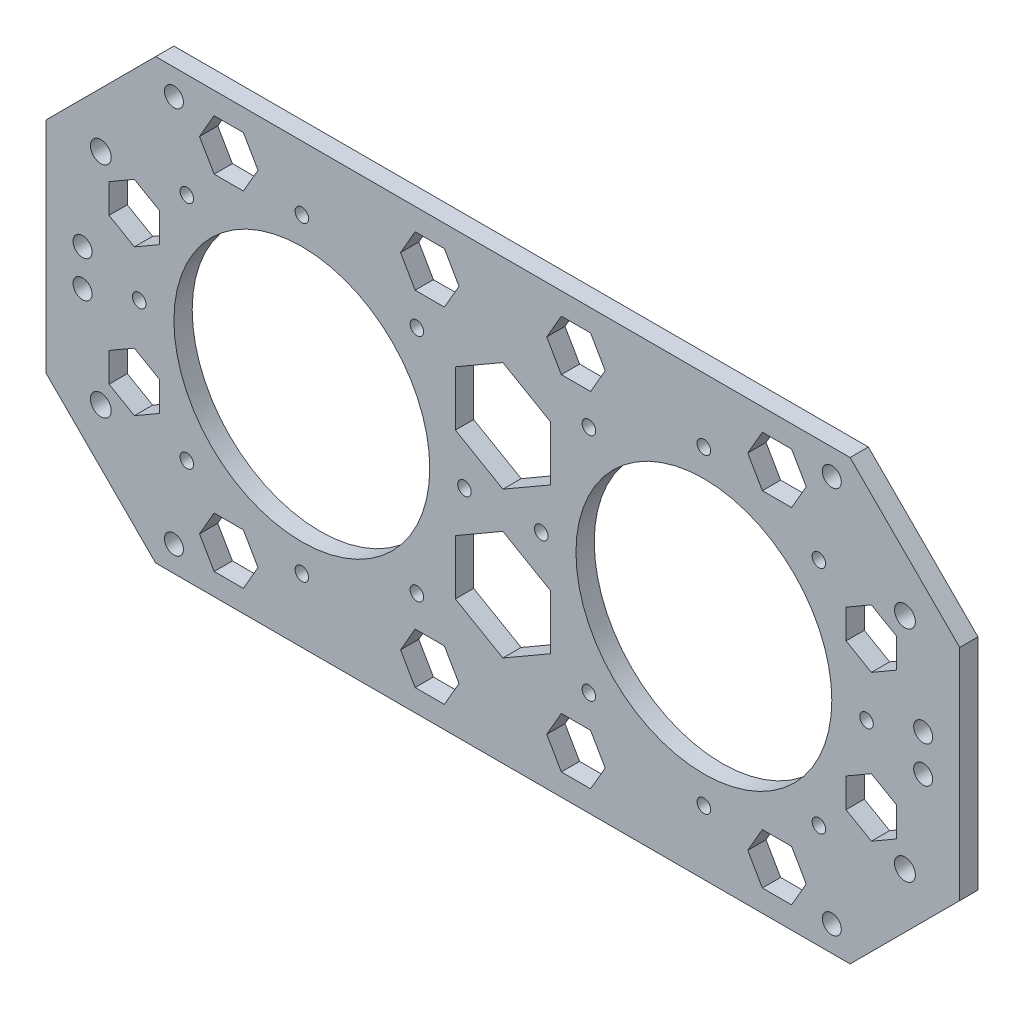
SolidWorks part; units mm, degrees
ref_plane "前视基准面" through (0, 0, 0) normal (0, 0, 1) x (1, 0, 0)
ref_plane "上视基准面" through (0, 0, 0) normal (0, 1, 0) x (1, 0, 0)
ref_plane "右视基准面" through (0, 0, 0) normal (1, 0, 0) x (0, 0, -1)
other "Configuration Table"
sketch "草图1" plane through (0, 0, 0) normal (0, 0, 1) x (1, 0, 0)
  line L1 (0, 0) -> (250, 0)
  line L2 (0, 0) -> (0, 120)
  line L3 (0, 120) -> (250, 120)
  line L4 (250, 0) -> (250, 120)
  circle A0 centre (70, 60) radius 35
  circle A1 centre (180, 60) radius 35
  dimension "D3" = 70
  dimension "D4" = 70
  dimension "D7" = 70
  dimension "D8" = 60
  dimension "D1" = 250
  dimension "D2" = 120
  dimension "D5" = 60
  dimension "D6" = 70
extrude "凸台-拉伸1" add sketch "草图1" along normal blind 5
sketch "草图2" plane through (0, 0, 5) normal (0, 0, 1) x (1, 0, 0)
  line L0 (125, 120) -> (125, 0) construction
  line L4 (0, 120) -> (0, 0)
  line L5 (0, 0) -> (250, 0)
  line L6 (250, 0) -> (250, 120)
  line L7 (250, 120) -> (0, 120)
  line L8 (0, 120) -> (0, 0)
  line L9 (0, 0) -> (250, 0)
  line L10 (250, 0) -> (250, 120)
  line L11 (250, 120) -> (0, 120)
  circle A0 centre (70, 102.5) radius 1.85
  circle A1 centre (70, 60) radius 35 construction
  circle A2 centre (70, 60) radius 35
  circle A3 centre (70, 17.5) radius 1.85
  circle A4 centre (25.5, 60) radius 1.85
  circle A5 centre (38.5337, 91.4663) radius 1.85
  circle A6 centre (70, 104.5) radius 1.85
  circle A7 centre (101.4663, 91.4663) radius 1.85
  circle A8 centre (114.5, 60) radius 1.85
  circle A9 centre (101.4663, 28.5337) radius 1.85
  circle A10 centre (70, 15.5) radius 1.85
  circle A11 centre (38.5337, 28.5337) radius 1.85
  circle A12 centre (180, 102.5) radius 1.85
  circle A13 centre (148.5337, 91.4663) radius 1.85
  circle A14 centre (135.5, 60) radius 1.85
  circle A15 centre (148.5337, 28.5337) radius 1.85
  circle A16 centre (180, 17.5) radius 1.85
  circle A17 centre (211.4663, 28.5337) radius 1.85
  circle A18 centre (224.5, 60) radius 1.85
  circle A19 centre (211.4663, 91.4663) radius 1.85
  point P14 (70, 60)
  point P30 (70, 60)
  dimension "D1" = 3.7
  dimension "D5" = 3.7
  dimension "D7" = 60
  dimension "D3" = 42.5
  dimension "D6" = 44.5
  dimension "D2" = 0
  dimension "D4" = 2
  dimension "D8" = 8
extrude "切除-拉伸1" cut sketch "草图2" against normal blind 10 contours A5 | A4 | A11 | A10 A3 | A3 A10 | A9 | A8 | A6 A0 | A0 A6 | A7 | A14 | A12 | A19 | A18 | A17 | A15 | A13 | A16 region at (70, 101.9688, 5) region at (70, 103.5, 5) region at (70, 18.0312, 5) region at (70, 16.5, 5) region at (25.5, 60, 5) region at (38.5337, 91.4663, 5) region at (101.4663, 91.4663, 5) region at (114.5, 60, 5) region at (101.4663, 28.5337, 5) region at (38.5337, 28.5337, 5) region at (180, 102.5, 5) region at (135.5, 60, 5) region at (148.5337, 28.5337, 5) region at (211.4663, 28.5337, 5) region at (224.5, 60, 5) region at (211.4663, 91.4663, 5)
sketch "草图3" plane through (0, 0, 5) normal (0, 0, 1) x (1, 0, 0)
  line L0 (30, 120) -> (0, 90)
  line L1 (125, 120) -> (125, 0)
  line L2 (0, 60) -> (250, 60)
  line L3 (220, 120) -> (250, 90)
  line L4 (0, 120) -> (0, 0)
  line L5 (0, 0) -> (250, 0)
  line L6 (250, 0) -> (250, 120)
  line L7 (250, 120) -> (0, 120)
  line L8 (0, 120) -> (0, 0)
  line L9 (0, 0) -> (250, 0)
  line L10 (250, 0) -> (250, 120)
  line L11 (250, 120) -> (0, 120)
  line L12 (220, 0) -> (250, 30)
  line L13 (30, 0) -> (0, 30)
  line M17 (0, 120) -> (0, 0)
  line M18 (0, 0) -> (250, 0)
  line M19 (250, 0) -> (250, 120)
  line M20 (250, 120) -> (0, 120)
  dimension "D2" = 45
  dimension "D3" = 30
  dimension "D1" = 0
extrude "切除-拉伸2" cut sketch "草图3" against normal blind 10 contours L0 M20 M17 | L13 L8 M18 | L12 L9 M19 | L3 M20 M19 region at (10, 110, 5) region at (240, 110, 5) region at (10, 10, 5) region at (240, 10, 5)
sketch "草图4" plane through (0, 0, 0) normal (0, 0, -1) x (-1, 0, 0)
  line L0 (-125, 120) -> (-125, 0) construction
  line L1 (-125, 65) -> (-112.0096, 72.5)
  line L2 (-112.0096, 72.5) -> (-112.0096, 87.5)
  line L3 (-112.0096, 87.5) -> (-125, 95)
  line L4 (-125, 95) -> (-137.9904, 87.5)
  line L5 (-137.9904, 87.5) -> (-137.9904, 72.5)
  line L6 (-137.9904, 72.5) -> (-125, 65)
  line L7 (-250, 60) -> (0, 60) construction
  line L8 (-220, 120) -> (-250, 90)
  line L9 (-250, 90) -> (-250, 30)
  line L10 (-250, 30) -> (-220, 0)
  line L11 (-220, 0) -> (-30, 0)
  line L12 (-30, 0) -> (0, 30)
  line L13 (0, 30) -> (0, 90)
  line L14 (0, 90) -> (-30, 120)
  line L15 (-30, 120) -> (-220, 120)
  line L16 (-220, 120) -> (-250, 90)
  line L17 (-250, 90) -> (-250, 30)
  line L18 (-250, 30) -> (-220, 0)
  line L19 (-220, 0) -> (-30, 0)
  line L20 (-30, 0) -> (0, 30)
  line L21 (0, 30) -> (0, 90)
  line L22 (0, 90) -> (-30, 120)
  line L23 (-30, 120) -> (-220, 120)
  line L24 (-109, 100.1436) -> (-113, 107.0718)
  line L25 (-137, 107.0718) -> (-141, 114)
  line L26 (-141, 114) -> (-149, 114)
  line L27 (-149, 114) -> (-153, 107.0718)
  line L28 (-153, 107.0718) -> (-149, 100.1436)
  line L29 (-149, 100.1436) -> (-141, 100.1436)
  line L30 (-141, 100.1436) -> (-137, 107.0718)
  line L31 (-101, 100.1436) -> (-109, 100.1436)
  line L32 (-97, 107.0718) -> (-101, 100.1436)
  line L33 (-101, 114) -> (-97, 107.0718)
  line L34 (-109, 114) -> (-101, 114)
  line L35 (-113, 107.0718) -> (-109, 114)
  line L36 (-137.9904, 47.5) -> (-125, 55)
  line L37 (-137.9904, 32.5) -> (-137.9904, 47.5)
  line L38 (-125, 25) -> (-137.9904, 32.5)
  line L39 (-112.0096, 32.5) -> (-125, 25)
  line L40 (-112.0096, 47.5) -> (-112.0096, 32.5)
  line L41 (-125, 55) -> (-112.0096, 47.5)
  line L42 (-101, 19.8564) -> (-109, 19.8564)
  line L43 (-97, 12.9282) -> (-101, 19.8564)
  line L44 (-101, 6) -> (-97, 12.9282)
  line L45 (-109, 6) -> (-101, 6)
  line L46 (-113, 12.9282) -> (-109, 6)
  line L47 (-109, 19.8564) -> (-113, 12.9282)
  line L48 (-141, 19.8564) -> (-137, 12.9282)
  line L49 (-149, 19.8564) -> (-141, 19.8564)
  line L50 (-153, 12.9282) -> (-149, 19.8564)
  line L51 (-149, 6) -> (-153, 12.9282)
  line L52 (-141, 6) -> (-149, 6)
  line L53 (-137, 12.9282) -> (-141, 6)
  circle A0 centre (-125, 80) radius 12.9904 construction
  circle A1 centre (-145, 107.0718) radius 6.9282 construction
  dimension "D2" = 15
  dimension "D3" = 40
  dimension "D4" = 6
  dimension "D5" = 8
  dimension "D6" = 20
  dimension "D1" = 0
extrude "切除-拉伸3" cut sketch "草图4" against normal blind 10 contours L25 L26 L27 L28 L29 L30 | L24 L35 L34 L33 L32 L31 | L1 L2 L3 L4 L5 L6 | L36 L41 L40 L39 L38 L37 | L48 L53 L52 L51 L50 L49 | L42 L47 L46 L45 L44 L43
sketch "草图6" plane through (0, 0, 5) normal (0, 0, 1) x (1, 0, 0)
  line L0 (220, 120) -> (250, 90) construction
  line L1 (250, 30) -> (250, 90) construction
  line L2 (220, 0) -> (250, 30) construction
  line L3 (30, 0) -> (220, 0) construction
  line L4 (220, 120) -> (30, 120) construction
  line L5 (30, 0) -> (0, 30) construction
  line L6 (141, 100.1436) -> (149, 100.1436)
  line L7 (137, 107.0718) -> (141, 100.1436)
  line L8 (141, 114) -> (137, 107.0718)
  line L9 (149, 114) -> (141, 114)
  line L10 (153, 107.0718) -> (149, 114)
  line L11 (149, 100.1436) -> (153, 107.0718)
  line L12 (141, 100.1436) -> (149, 100.1436)
  line L13 (137, 107.0718) -> (141, 100.1436)
  line L14 (141, 114) -> (137, 107.0718)
  line L15 (149, 114) -> (141, 114)
  line L16 (153, 107.0718) -> (149, 114)
  line L17 (149, 100.1436) -> (153, 107.0718)
  line L18 (97, 12.9282) -> (101, 6)
  line L19 (101, 19.8564) -> (97, 12.9282)
  line L20 (109, 19.8564) -> (101, 19.8564)
  line L21 (113, 12.9282) -> (109, 19.8564)
  line L22 (109, 6) -> (113, 12.9282)
  line L23 (101, 6) -> (109, 6)
  line L24 (97, 12.9282) -> (101, 6)
  line L25 (101, 19.8564) -> (97, 12.9282)
  line L26 (109, 19.8564) -> (101, 19.8564)
  line L27 (113, 12.9282) -> (109, 19.8564)
  line L28 (109, 6) -> (113, 12.9282)
  line L29 (101, 6) -> (109, 6)
  line L30 (149, 19.8564) -> (141, 19.8564)
  line L31 (153, 12.9282) -> (149, 19.8564)
  line L32 (149, 6) -> (153, 12.9282)
  line L33 (141, 6) -> (149, 6)
  line L34 (137, 12.9282) -> (141, 6)
  line L35 (141, 19.8564) -> (137, 12.9282)
  line L36 (149, 19.8564) -> (141, 19.8564)
  line L37 (153, 12.9282) -> (149, 19.8564)
  line L38 (149, 6) -> (153, 12.9282)
  line L39 (141, 6) -> (149, 6)
  line L40 (137, 12.9282) -> (141, 6)
  line L41 (141, 19.8564) -> (137, 12.9282)
  line L42 (137.9904, 32.5) -> (137.9904, 47.5)
  line L43 (125, 25) -> (137.9904, 32.5)
  line L44 (112.0096, 32.5) -> (125, 25)
  line L45 (112.0096, 47.5) -> (112.0096, 32.5)
  line L46 (125, 55) -> (112.0096, 47.5)
  line L47 (137.9904, 47.5) -> (125, 55)
  line L48 (137.9904, 32.5) -> (137.9904, 47.5)
  line L49 (125, 25) -> (137.9904, 32.5)
  line L50 (112.0096, 32.5) -> (125, 25)
  line L51 (112.0096, 47.5) -> (112.0096, 32.5)
  line L52 (125, 55) -> (112.0096, 47.5)
  line L53 (137.9904, 47.5) -> (125, 55)
  line L54 (137.9904, 72.5) -> (137.9904, 87.5)
  line L55 (125, 65) -> (137.9904, 72.5)
  line L56 (112.0096, 72.5) -> (125, 65)
  line L57 (112.0096, 87.5) -> (112.0096, 72.5)
  line L58 (125, 95) -> (112.0096, 87.5)
  line L59 (137.9904, 87.5) -> (125, 95)
  line L60 (137.9904, 72.5) -> (137.9904, 87.5)
  line L61 (125, 65) -> (137.9904, 72.5)
  line L62 (112.0096, 72.5) -> (125, 65)
  line L63 (112.0096, 87.5) -> (112.0096, 72.5)
  line L64 (125, 95) -> (112.0096, 87.5)
  line L65 (137.9904, 87.5) -> (125, 95)
  line L66 (101, 100.1436) -> (109, 100.1436)
  line L67 (97, 107.0718) -> (101, 100.1436)
  line L68 (101, 114) -> (97, 107.0718)
  line L69 (109, 114) -> (101, 114)
  line L70 (113, 107.0718) -> (109, 114)
  line L71 (109, 100.1436) -> (113, 107.0718)
  line L72 (101, 100.1436) -> (109, 100.1436)
  line L73 (97, 107.0718) -> (101, 100.1436)
  line L74 (101, 114) -> (97, 107.0718)
  line L75 (109, 114) -> (101, 114)
  line L76 (113, 107.0718) -> (109, 114)
  line L77 (109, 100.1436) -> (113, 107.0718)
  line L78 (0, 90) -> (0, 30) construction
  line L79 (30, 120) -> (0, 90) construction
  line L80 (220, 120) -> (250, 90)
  line L81 (250, 30) -> (250, 90)
  line L82 (220, 0) -> (250, 30)
  line L83 (30, 0) -> (220, 0)
  line L84 (220, 120) -> (30, 120)
  line L85 (30, 0) -> (0, 30)
  line L86 (0, 90) -> (0, 30)
  line L87 (30, 120) -> (0, 90)
  circle A1 centre (70, 60) radius 35
  circle A2 centre (70, 60) radius 35
  circle A3 centre (180, 60) radius 35
  circle A4 centre (180, 60) radius 35
  circle A5 centre (38.5337, 91.4663) radius 1.85
  circle A6 centre (38.5337, 91.4663) radius 1.85
  circle A7 centre (114.5, 60) radius 1.85
  circle A8 centre (114.5, 60) radius 1.85
  circle A9 centre (70, 102.5) radius 1.85
  circle A10 centre (70, 102.5) radius 1.85
  circle A11 centre (101.4663, 91.4663) radius 1.85
  circle A12 centre (101.4663, 91.4663) radius 1.85
  circle A13 centre (135.5, 60) radius 1.85
  circle A14 centre (135.5, 60) radius 1.85
  circle A15 centre (101.4663, 28.5337) radius 1.85
  circle A16 centre (101.4663, 28.5337) radius 1.85
  circle A17 centre (70, 17.5) radius 1.85
  circle A18 centre (70, 17.5) radius 1.85
  circle A19 centre (38.5337, 28.5337) radius 1.85
  circle A20 centre (38.5337, 28.5337) radius 1.85
  circle A21 centre (25.5, 60) radius 1.85
  circle A22 centre (25.5, 60) radius 1.85
  circle A23 centre (180, 17.5) radius 1.85
  circle A24 centre (180, 17.5) radius 1.85
  circle A25 centre (148.5337, 91.4663) radius 1.85
  circle A26 centre (148.5337, 91.4663) radius 1.85
  circle A27 centre (148.5337, 28.5337) radius 1.85
  circle A28 centre (148.5337, 28.5337) radius 1.85
  circle A29 centre (211.4663, 28.5337) radius 1.85
  circle A30 centre (211.4663, 28.5337) radius 1.85
  circle A31 centre (224.5, 60) radius 1.85
  circle A32 centre (224.5, 60) radius 1.85
  circle A33 centre (211.4663, 91.4663) radius 1.85
  circle A34 centre (211.4663, 91.4663) radius 1.85
  circle A35 centre (180, 102.5) radius 1.85
  circle A36 centre (180, 102.5) radius 1.85
  dimension "D1" = 0
  dimension "D2" = 0
  dimension "D3" = 0
  dimension "D4" = 0
  dimension "D5" = 0
  dimension "D6" = 0
  dimension "D7" = 0
  dimension "D8" = 0
  dimension "D9" = 0
  dimension "D10" = 0
  dimension "D11" = 0
  dimension "D12" = 0
  dimension "D13" = 0
  dimension "D14" = 0
  dimension "D15" = 0
  dimension "D16" = 0
  dimension "D17" = 0
  dimension "D18" = 0
  dimension "D19" = 0
  dimension "D20" = 0
  dimension "D21" = 0
  dimension "D22" = 0
  dimension "D23" = 0
  dimension "D24" = 0
sketch "草图7" plane through (0, 0, 5) normal (0, 0, 1) x (1, 0, 0)
  line L0 (125, 120) -> (125, 0) construction
  line L1 (65, 0) -> (95, 0)
  line L2 (65, 0) -> (65, -5)
  line L3 (65, -5) -> (95, -5)
  line L4 (95, 0) -> (95, -5)
  line L5 (155, 0) -> (185, 0)
  line L6 (155, 0) -> (155, -5)
  line L7 (155, -5) -> (185, -5)
  line L8 (250, 30) -> (250, 90)
  line L9 (250, 90) -> (220, 120)
  line L10 (220, 120) -> (30, 120)
  line L11 (30, 120) -> (0, 90)
  line L12 (0, 90) -> (0, 30)
  line L13 (0, 30) -> (30, 0)
  line L14 (30, 0) -> (220, 0)
  line L15 (220, 0) -> (250, 30)
  line L16 (250, 30) -> (250, 90)
  line L17 (250, 90) -> (220, 120)
  line L18 (220, 120) -> (30, 120)
  line L19 (30, 120) -> (0, 90)
  line L20 (0, 90) -> (0, 30)
  line L21 (0, 30) -> (30, 0)
  line L22 (30, 0) -> (220, 0)
  line L23 (220, 0) -> (250, 30)
  line L24 (185, 0) -> (185, -5)
  line L25 (0, 60) -> (250, 60) construction
  line L26 (185, 120) -> (185, 125)
  line L27 (155, 125) -> (185, 125)
  line L28 (155, 120) -> (155, 125)
  line L29 (95, 120) -> (95, 125)
  line L30 (65, 125) -> (95, 125)
  line L31 (65, 120) -> (65, 125)
  dimension "D2" = 30
  dimension "D3" = 5
  dimension "D4" = 30
  dimension "D5" = 30
  dimension "D6" = 5
  dimension "D7" = 30
  dimension "D1" = 0
extrude "凸台-拉伸2" add sketch "草图7" against normal blind 5 contours L31 L18 L29 L30 | L28 L18 L26 L27 | L4 L1 L2 L3 | L24 L5 L6 L7 region at (80, -2.5, 5) region at (170, -2.5, 5) region at (80, 122.5, 5) region at (170, 122.5, 5)
sketch "草图8" plane through (0, 0, 5) normal (0, 0, 1) x (1, 0, 0)
  line L24 (250, 30) -> (250, 90)
  line L25 (250, 90) -> (220, 120)
  line L26 (220, 120) -> (185, 120)
  line L27 (185, 120) -> (185, 125)
  line L28 (185, 120) -> (185, 125)
  line L29 (185, 125) -> (155, 125)
  line L30 (185, 125) -> (155, 125)
  line L31 (155, 125) -> (155, 120)
  line L32 (155, 125) -> (155, 120)
  line L33 (155, 120) -> (95, 120)
  line L34 (155, 120) -> (95, 120)
  line L35 (30, 120) -> (0, 90)
  line L36 (0, 90) -> (0, 30)
  line L37 (0, 30) -> (30, 0)
  line L38 (30, 0) -> (65, 0)
  line L39 (95, 120) -> (95, 125)
  line L40 (95, 120) -> (95, 125)
  line L41 (95, 125) -> (65, 125)
  line L42 (95, 125) -> (65, 125)
  line L43 (65, 125) -> (65, 120)
  line L44 (65, 125) -> (65, 120)
  line L45 (65, 120) -> (30, 120)
  line L46 (65, 120) -> (30, 120)
  line L47 (220, 0) -> (250, 30)
  line L48 (250, 30) -> (250, 90)
  line L49 (250, 90) -> (220, 120)
  line L50 (220, 120) -> (185, 120)
  line L59 (30, 120) -> (0, 90)
  line L60 (0, 90) -> (0, 30)
  line L61 (0, 30) -> (30, 0)
  line L62 (30, 0) -> (65, 0)
  line L71 (220, 0) -> (250, 30)
  line L72 (65, 0) -> (65, -5)
  line L73 (65, 0) -> (65, -5)
  line L74 (65, -5) -> (95, -5)
  line L75 (65, -5) -> (95, -5)
  line L76 (95, -5) -> (95, 0)
  line L77 (95, -5) -> (95, 0)
  line L78 (95, 0) -> (155, 0)
  line L79 (95, 0) -> (155, 0)
  line L80 (155, 0) -> (155, -5)
  line L81 (155, 0) -> (155, -5)
  line L82 (155, -5) -> (185, -5)
  line L83 (155, -5) -> (185, -5)
  line L84 (185, -5) -> (185, 0)
  line L85 (185, -5) -> (185, 0)
  line L86 (185, 0) -> (220, 0)
  line L87 (185, 0) -> (220, 0)
  circle A0 centre (65, 0) radius 1
  circle A1 centre (95, 0) radius 1
  circle A2 centre (155, 0) radius 1
  circle A3 centre (185, 0) radius 1
  circle A4 centre (65, 120) radius 1
  circle A5 centre (95, 120) radius 1
  circle A6 centre (155, 120) radius 1
  circle A7 centre (185, 120) radius 1
  dimension "D2" = 2
  dimension "D3" = 2
  dimension "D4" = 2
  dimension "D5" = 2
  dimension "D6" = 2
  dimension "D7" = 2
  dimension "D8" = 2
  dimension "D9" = 2
  dimension "D1" = 0
extrude "切除-拉伸4" cut sketch "草图8" against normal blind 10 contours L79 A1 L77 | L81 A2 L79 | L87 A3 L85 | L34 A6 L32 | L28 A7 L50 | L46 A4 L44 | L40 A5 L34 | A0 region at (184.8585, 0.1415, 5) region at (184.8585, 119.8585, 5) region at (155.1415, 0.1415, 5) region at (155.1415, 119.8585, 5) region at (94.8585, 0.1415, 5) region at (94.8585, 119.8585, 5) region at (65.1415, 119.8585, 5)
sketch "草图9" plane through (0, 0, 5) normal (0, 0, 1) x (1, 0, 0)
  line L0 (125, 120) -> (125, 0) construction
  line L1 (0, 75) -> (5, 75)
  line L2 (0, 75) -> (0, 45)
  line L3 (0, 45) -> (5, 45)
  line L4 (5, 75) -> (5, 45)
  line L5 (250, 45) -> (245, 45)
  line L6 (245, 75) -> (245, 45)
  line L7 (250, 75) -> (250, 45)
  line L8 (250, 75) -> (245, 75)
  line L28 (96, 0) -> (154, 0)
  line L34 (30, 0) -> (64, 0)
  line L35 (30, 0) -> (64, 0)
  line L36 (65, -1) -> (65, -5)
  line L37 (65, -1) -> (65, -5)
  line L38 (65, -5) -> (95, -5)
  line L39 (65, -5) -> (95, -5)
  line L40 (95, -5) -> (95, -1)
  line L41 (95, -5) -> (95, -1)
  line L42 (155, -1) -> (155, -5)
  line L43 (155, -1) -> (155, -5)
  line L44 (155, -5) -> (185, -5)
  line L45 (155, -5) -> (185, -5)
  line L46 (185, -5) -> (185, -1)
  line L47 (185, -5) -> (185, -1)
  line L72 (186, 0) -> (220, 0)
  line L73 (186, 0) -> (220, 0)
  line L74 (220, 0) -> (250, 30)
  line L75 (220, 0) -> (250, 30)
  line L76 (250, 30) -> (250, 90)
  line L77 (250, 30) -> (250, 90)
  line L78 (250, 90) -> (220, 120)
  line L79 (250, 90) -> (220, 120)
  line L80 (220, 120) -> (186, 120)
  line L81 (220, 120) -> (186, 120)
  line L82 (185, 121) -> (185, 125)
  line L83 (185, 121) -> (185, 125)
  line L84 (185, 125) -> (155, 125)
  line L85 (185, 125) -> (155, 125)
  line L86 (155, 125) -> (155, 121)
  line L87 (155, 125) -> (155, 121)
  line L88 (96, 0) -> (154, 0)
  line L90 (95, 121) -> (95, 125)
  line L91 (95, 121) -> (95, 125)
  line L92 (95, 125) -> (65, 125)
  line L93 (95, 125) -> (65, 125)
  line L94 (65, 125) -> (65, 121)
  line L95 (65, 125) -> (65, 121)
  line L96 (64, 120) -> (30, 120)
  line L97 (64, 120) -> (30, 120)
  line L98 (30, 120) -> (0, 90)
  line L99 (30, 120) -> (0, 90)
  line L100 (0, 90) -> (0, 30)
  line L101 (0, 90) -> (0, 30)
  line L102 (0, 30) -> (30, 0)
  line L103 (0, 30) -> (30, 0)
  line L104 (154, 120) -> (96, 120)
  line L105 (154, 120) -> (96, 120)
  circle A0 centre (5, 75) radius 1
  circle A1 centre (5, 45) radius 1
  circle A2 centre (245, 75) radius 1
  circle A3 centre (245, 45) radius 1
  arc A12 (65, -1) -> (64, 0) centre (65, 0) ccw
  arc A13 (65, -1) -> (64, 0) centre (65, 0) ccw
  arc A15 (96, 0) -> (95, -1) centre (95, 0) ccw
  arc A25 (96, 0) -> (95, -1) centre (95, 0) ccw
  arc A27 (155, -1) -> (154, 0) centre (155, 0) ccw
  arc A29 (155, -1) -> (154, 0) centre (155, 0) ccw
  arc A31 (186, 0) -> (185, -1) centre (185, 0) ccw
  arc A33 (186, 0) -> (185, -1) centre (185, 0) ccw
  arc A35 (185, 121) -> (186, 120) centre (185, 120) ccw
  arc A36 (185, 121) -> (186, 120) centre (185, 120) ccw
  arc A37 (154, 120) -> (155, 121) centre (155, 120) ccw
  arc A38 (154, 120) -> (155, 121) centre (155, 120) ccw
  arc A39 (95, 121) -> (96, 120) centre (95, 120) ccw
  arc A40 (95, 121) -> (96, 120) centre (95, 120) ccw
  arc A41 (64, 120) -> (65, 121) centre (65, 120) ccw
  arc A42 (64, 120) -> (65, 121) centre (65, 120) ccw
  dimension "D5" = 2
  dimension "D6" = 2
  dimension "D7" = 2
  dimension "D8" = 2
  dimension "D2" = 5
  dimension "D3" = 30
  dimension "D1" = 0
extrude "切除-拉伸5" cut sketch "草图9" against normal blind 5 contours A1 L4 A0 L1 L2 L3 | L1 A0 L4 | L4 A0 L1 | L4 A1 L3 | L3 A1 L4 | L8 A2 L6 | A3 L5 L7 L8 A2 L6 | L6 A2 L8 | L6 A3 L5 | L5 A3 L6 region at (2.478, 60, 5) region at (5.1415, 75.1415, 5) region at (4.5756, 74.5756, 5) region at (4.5756, 45.4244, 5) region at (5.1415, 44.8585, 5) region at (247.522, 60, 5) region at (245.4244, 74.5756, 5) region at (244.8585, 75.1415, 5) region at (244.8585, 44.8585, 5) region at (245.4244, 45.4244, 5)
sketch "草图10" plane through (0, 0, 5) normal (0, 0, 1) x (1, 0, 0)
  line L0 (60, 0) -> (60, 16.3528)
  line L1 (125, 120) -> (125, 0)
  line L2 (5, 60) -> (245, 60)
  line L32 (4, 45) -> (0, 45)
  line L33 (0, 45) -> (0, 30)
  line L34 (0, 30) -> (30, 0)
  line L35 (30, 0) -> (64, 0)
  line L36 (65, -1) -> (65, -5)
  line L37 (65, -5) -> (95, -5)
  line L38 (95, -5) -> (95, -1)
  line L39 (96, 0) -> (154, 0)
  line L40 (155, -1) -> (155, -5)
  line L41 (155, -5) -> (185, -5)
  line L42 (185, -5) -> (185, -1)
  line L43 (186, 0) -> (220, 0)
  line L44 (220, 0) -> (250, 30)
  line L45 (250, 30) -> (250, 45)
  line L46 (250, 45) -> (246, 45)
  line L47 (245, 46) -> (245, 74)
  line L48 (246, 75) -> (250, 75)
  line L49 (250, 75) -> (250, 90)
  line L50 (250, 90) -> (220, 120)
  line L51 (220, 120) -> (186, 120)
  line L52 (185, 121) -> (185, 125)
  line L53 (185, 125) -> (155, 125)
  line L54 (155, 125) -> (155, 121)
  line L55 (96, 0) -> (154, 0)
  line L56 (95, 121) -> (95, 125)
  line L57 (95, 125) -> (65, 125)
  line L58 (65, 125) -> (65, 121)
  line L59 (64, 120) -> (30, 120)
  line L60 (30, 120) -> (0, 90)
  line L61 (0, 90) -> (0, 75)
  line L62 (0, 75) -> (4, 75)
  line L63 (5, 74) -> (5, 46)
  line L64 (4, 45) -> (0, 45)
  line L65 (0, 45) -> (0, 30)
  line L66 (0, 30) -> (30, 0)
  line L67 (30, 0) -> (64, 0)
  line L68 (65, -1) -> (65, -5)
  line L69 (65, -5) -> (95, -5)
  line L70 (95, -5) -> (95, -1)
  line L72 (155, -1) -> (155, -5)
  line L73 (155, -5) -> (185, -5)
  line L74 (185, -5) -> (185, -1)
  line L75 (186, 0) -> (220, 0)
  line L76 (220, 0) -> (250, 30)
  line L77 (250, 30) -> (250, 45)
  line L78 (250, 45) -> (246, 45)
  line L79 (245, 46) -> (245, 74)
  line L80 (246, 75) -> (250, 75)
  line L81 (250, 75) -> (250, 90)
  line L82 (250, 90) -> (220, 120)
  line L83 (220, 120) -> (186, 120)
  line L84 (185, 121) -> (185, 125)
  line L85 (185, 125) -> (155, 125)
  line L86 (155, 125) -> (155, 121)
  line L88 (95, 121) -> (95, 125)
  line L89 (95, 125) -> (65, 125)
  line L90 (65, 125) -> (65, 121)
  line L91 (64, 120) -> (30, 120)
  line L92 (30, 120) -> (0, 90)
  line L93 (0, 90) -> (0, 75)
  line L94 (0, 75) -> (4, 75)
  line L95 (5, 74) -> (5, 46)
  line L99 (154, 120) -> (96, 120)
  line L100 (154, 120) -> (96, 120)
  circle A0 centre (15, 30) radius 2.85
  circle A1 centre (10, 55) radius 2.6
  circle A2 centre (35, 7) radius 2.6
  circle A3 centre (215, 7) radius 2.6
  circle A4 centre (235, 30) radius 2.85
  circle A5 centre (240, 55) radius 2.6
  circle A6 centre (240, 65) radius 2.6
  circle A7 centre (235, 90) radius 2.85
  circle A8 centre (215, 113) radius 2.6
  circle A9 centre (35, 113) radius 2.6
  circle A10 centre (15, 90) radius 2.85
  circle A11 centre (10, 65) radius 2.6
  arc A12 (4, 45) -> (5, 46) centre (5, 45) ccw
  arc A17 (245, 46) -> (246, 45) centre (245, 45) ccw
  arc A18 (246, 75) -> (245, 74) centre (245, 75) ccw
  arc A23 (5, 74) -> (4, 75) centre (5, 75) ccw
  arc A24 (4, 45) -> (5, 46) centre (5, 45) ccw
  arc A29 (245, 46) -> (246, 45) centre (245, 45) ccw
  arc A30 (246, 75) -> (245, 74) centre (245, 75) ccw
  arc A35 (5, 74) -> (4, 75) centre (5, 75) ccw
  arc A40 (65, -1) -> (64, 0) centre (65, 0) ccw
  arc A41 (65, -1) -> (64, 0) centre (65, 0) ccw
  arc A42 (96, 0) -> (95, -1) centre (95, 0) ccw
  arc A43 (96, 0) -> (95, -1) centre (95, 0) ccw
  arc A44 (155, -1) -> (154, 0) centre (155, 0) ccw
  arc A45 (155, -1) -> (154, 0) centre (155, 0) ccw
  arc A46 (186, 0) -> (185, -1) centre (185, 0) ccw
  arc A47 (186, 0) -> (185, -1) centre (185, 0) ccw
  arc A48 (185, 121) -> (186, 120) centre (185, 120) ccw
  arc A49 (185, 121) -> (186, 120) centre (185, 120) ccw
  arc A50 (154, 120) -> (155, 121) centre (155, 120) ccw
  arc A51 (154, 120) -> (155, 121) centre (155, 120) ccw
  arc A52 (95, 121) -> (96, 120) centre (95, 120) ccw
  arc A53 (95, 121) -> (96, 120) centre (95, 120) ccw
  arc A54 (64, 120) -> (65, 121) centre (65, 120) ccw
  arc A55 (64, 120) -> (65, 121) centre (65, 120) ccw
  dimension "D3" = 5.7
  dimension "D4" = 0
  dimension "D5" = 5.2
  dimension "D10" = 5.2
  dimension "D2" = 15
  dimension "D6" = 10
  dimension "D7" = 10
  dimension "D8" = 30
  dimension "D9" = 25
  dimension "D11" = 7
  dimension "D1" = 0
extrude "切除-拉伸6" cut sketch "草图10" against normal through all contours A1 | A0 | A2 | A3 | A4 | A5 | A11 | A10 | A9 | A8 | A7 | A6 region at (15, 30, 5) region at (10, 55, 5) region at (35, 7, 5) region at (215, 7, 5) region at (235, 30, 5) region at (240, 55, 5)
sketch "草图11" plane through (0, 0, 0) normal (0, 0, -1) x (-1, 0, 0)
  line L1 (-218.8976, 76) -> (-218.8976, 84)
  line L2 (-218.8976, 84) -> (-225.8258, 88)
  line L3 (-225.8258, 88) -> (-232.754, 84)
  line L4 (-232.754, 84) -> (-232.754, 76)
  line L5 (-232.754, 76) -> (-225.8258, 72)
  line L6 (-225.8258, 72) -> (-218.8976, 76)
  line L8 (-220, 120) -> (-186, 120) construction
  line L9 (-245, 60) -> (-5, 60)
  line L10 (-245, 74) -> (-245, 46) construction
  line L11 (-5, 74) -> (-5, 46) construction
  line L12 (-225.8258, 48) -> (-218.8976, 44)
  line L13 (-232.754, 44) -> (-225.8258, 48)
  line L14 (-232.754, 36) -> (-232.754, 44)
  line L15 (-225.8258, 32) -> (-232.754, 36)
  line L16 (-218.8976, 36) -> (-225.8258, 32)
  line L17 (-218.8976, 44) -> (-218.8976, 36)
  line L18 (-125, 120) -> (-125, 0)
  line L19 (-154, 120) -> (-96, 120) construction
  line L20 (-96, 0) -> (-154, 0) construction
  line L21 (-17.246, 44) -> (-24.1742, 48)
  line L22 (-17.246, 36) -> (-17.246, 44)
  line L23 (-24.1742, 32) -> (-17.246, 36)
  line L24 (-31.1024, 36) -> (-24.1742, 32)
  line L25 (-31.1024, 44) -> (-31.1024, 36)
  line L26 (-24.1742, 48) -> (-31.1024, 44)
  line L27 (-24.1742, 72) -> (-31.1024, 76)
  line L28 (-17.246, 76) -> (-24.1742, 72)
  line L29 (-17.246, 84) -> (-17.246, 76)
  line L30 (-24.1742, 88) -> (-17.246, 84)
  line L31 (-31.1024, 84) -> (-24.1742, 88)
  line L32 (-31.1024, 76) -> (-31.1024, 84)
  circle A0 centre (-225.8258, 80) radius 6.9282 construction
  circle A1 centre (-180, 60) radius 35 construction
  circle A2 centre (-180, 60) radius 35
  dimension "D1" = 8
  dimension "D2" = 50
  dimension "D3" = 32
extrude "切除-拉伸7" cut sketch "草图11" against normal blind 10 contours L5 L6 L1 L2 L3 L4 | L17 L12 L13 L14 L15 L16 | L32 L27 L28 L29 L30 L31 | L21 L26 L25 L24 L23 L22 region at (225.8258, 80, 0) region at (225.8258, 40, 0) region at (24.1742, 40, 0) region at (24.1742, 80, 0)
sketch "草图12" plane through (0, 0, 5) normal (0, 0, 1) x (1, 0, 0)
  line L1 (58, 107.0718) -> (54, 114)
  line L2 (54, 114) -> (46, 114)
  line L3 (46, 114) -> (42, 107.0718)
  line L4 (42, 107.0718) -> (46, 100.1436)
  line L5 (46, 100.1436) -> (54, 100.1436)
  line L6 (54, 100.1436) -> (58, 107.0718)
  line L7 (64, 120) -> (30, 120) construction
  line L8 (0, 90) -> (0, 75) construction
  line L9 (5, 60) -> (245, 60)
  line L10 (5, 74) -> (5, 46) construction
  line L11 (245, 74) -> (245, 46) construction
  line L12 (125, 120) -> (125, 0)
  line L13 (154, 120) -> (96, 120) construction
  line L14 (96, 0) -> (154, 0) construction
  line L15 (196, 100.1436) -> (192, 107.0718)
  line L16 (204, 100.1436) -> (196, 100.1436)
  line L17 (208, 107.0718) -> (204, 100.1436)
  line L18 (204, 114) -> (208, 107.0718)
  line L19 (196, 114) -> (204, 114)
  line L20 (192, 107.0718) -> (196, 114)
  line L21 (204, 19.8564) -> (196, 19.8564)
  line L22 (208, 12.9282) -> (204, 19.8564)
  line L23 (204, 6) -> (208, 12.9282)
  line L24 (196, 6) -> (204, 6)
  line L25 (192, 12.9282) -> (196, 6)
  line L26 (196, 19.8564) -> (192, 12.9282)
  line L27 (54, 19.8564) -> (58, 12.9282)
  line L28 (46, 19.8564) -> (54, 19.8564)
  line L29 (42, 12.9282) -> (46, 19.8564)
  line L30 (46, 6) -> (42, 12.9282)
  line L31 (54, 6) -> (46, 6)
  line L32 (58, 12.9282) -> (54, 6)
  circle A0 centre (50, 107.0718) radius 6.9282 construction
  dimension "D1" = 8
  dimension "D2" = 6
  dimension "D3" = 50
extrude "切除-拉伸8" cut sketch "草图12" against normal blind 10 contours L5 L6 L1 L2 L3 L4 | L32 L27 L28 L29 L30 L31 | L21 L26 L25 L24 L23 L22 | L20 L15 L16 L17 L18 L19 region at (50, 107.0718, 5) region at (200, 107.0718, 5) region at (200, 12.9282, 5) region at (50, 12.9282, 5)
sketch "草图13" plane through (0, 0, 5) normal (0, 0, 1) x (1, 0, 0)
  line L0 (64, 120) -> (96, 120)
  line L1 (154, 120) -> (186, 120)
  line L2 (64, 0) -> (96, 0)
  line L3 (154, 0) -> (186, 0)
  line L32 (4, 45) -> (0, 45)
  line L33 (0, 45) -> (0, 30)
  line L34 (0, 30) -> (30, 0)
  line L35 (30, 0) -> (64, 0)
  line L36 (65, -1) -> (65, -5)
  line L37 (65, -5) -> (95, -5)
  line L38 (95, -5) -> (95, -1)
  line L39 (96, 0) -> (154, 0)
  line L40 (155, -1) -> (155, -5)
  line L41 (155, -5) -> (185, -5)
  line L42 (185, -5) -> (185, -1)
  line L43 (186, 0) -> (220, 0)
  line L44 (220, 0) -> (250, 30)
  line L45 (250, 30) -> (250, 45)
  line L46 (250, 45) -> (246, 45)
  line L47 (245, 46) -> (245, 74)
  line L48 (246, 75) -> (250, 75)
  line L49 (250, 75) -> (250, 90)
  line L50 (250, 90) -> (220, 120)
  line L51 (220, 120) -> (186, 120)
  line L52 (185, 121) -> (185, 125)
  line L53 (185, 125) -> (155, 125)
  line L54 (155, 125) -> (155, 121)
  line L55 (96, 0) -> (154, 0)
  line L56 (95, 121) -> (95, 125)
  line L57 (95, 125) -> (65, 125)
  line L58 (65, 125) -> (65, 121)
  line L59 (64, 120) -> (30, 120)
  line L60 (30, 120) -> (0, 90)
  line L61 (0, 90) -> (0, 75)
  line L62 (0, 75) -> (4, 75)
  line L63 (5, 74) -> (5, 46)
  line L64 (4, 45) -> (0, 45)
  line L65 (0, 45) -> (0, 30)
  line L66 (0, 30) -> (30, 0)
  line L67 (30, 0) -> (64, 0)
  line L68 (65, -1) -> (65, -5)
  line L69 (65, -5) -> (95, -5)
  line L70 (95, -5) -> (95, -1)
  line L72 (155, -1) -> (155, -5)
  line L73 (155, -5) -> (185, -5)
  line L74 (185, -5) -> (185, -1)
  line L75 (186, 0) -> (220, 0)
  line L76 (220, 0) -> (250, 30)
  line L77 (250, 30) -> (250, 45)
  line L78 (250, 45) -> (246, 45)
  line L79 (245, 46) -> (245, 74)
  line L80 (246, 75) -> (250, 75)
  line L81 (250, 75) -> (250, 90)
  line L82 (250, 90) -> (220, 120)
  line L83 (220, 120) -> (186, 120)
  line L84 (185, 121) -> (185, 125)
  line L85 (185, 125) -> (155, 125)
  line L86 (155, 125) -> (155, 121)
  line L88 (95, 121) -> (95, 125)
  line L89 (95, 125) -> (65, 125)
  line L90 (65, 125) -> (65, 121)
  line L91 (64, 120) -> (30, 120)
  line L92 (30, 120) -> (0, 90)
  line L93 (0, 90) -> (0, 75)
  line L94 (0, 75) -> (4, 75)
  line L95 (5, 74) -> (5, 46)
  line L96 (154, 120) -> (96, 120)
  line L97 (154, 120) -> (96, 120)
  arc A12 (4, 45) -> (5, 46) centre (5, 45) ccw
  arc A13 (65, -1) -> (64, 0) centre (65, 0) ccw
  arc A14 (65, -1) -> (64, 0) centre (65, 0) ccw
  arc A15 (96, 0) -> (95, -1) centre (95, 0) ccw
  arc A16 (96, 0) -> (95, -1) centre (95, 0) ccw
  arc A17 (245, 46) -> (246, 45) centre (245, 45) ccw
  arc A18 (246, 75) -> (245, 74) centre (245, 75) ccw
  arc A19 (155, -1) -> (154, 0) centre (155, 0) ccw
  arc A20 (155, -1) -> (154, 0) centre (155, 0) ccw
  arc A21 (186, 0) -> (185, -1) centre (185, 0) ccw
  arc A22 (186, 0) -> (185, -1) centre (185, 0) ccw
  arc A23 (5, 74) -> (4, 75) centre (5, 75) ccw
  arc A24 (4, 45) -> (5, 46) centre (5, 45) ccw
  arc A29 (245, 46) -> (246, 45) centre (245, 45) ccw
  arc A30 (246, 75) -> (245, 74) centre (245, 75) ccw
  arc A35 (5, 74) -> (4, 75) centre (5, 75) ccw
  arc A36 (185, 121) -> (186, 120) centre (185, 120) ccw
  arc A37 (185, 121) -> (186, 120) centre (185, 120) ccw
  arc A38 (154, 120) -> (155, 121) centre (155, 120) ccw
  arc A39 (154, 120) -> (155, 121) centre (155, 120) ccw
  arc A40 (95, 121) -> (96, 120) centre (95, 120) ccw
  arc A41 (95, 121) -> (96, 120) centre (95, 120) ccw
  arc A42 (64, 120) -> (65, 121) centre (65, 120) ccw
  arc A43 (64, 120) -> (65, 121) centre (65, 120) ccw
  dimension "D1" = 0
sketch "草图14" plane through (0, 0, 5) normal (0, 0, 1) x (1, 0, 0)
  line L0 (0, 75) -> (0, 45)
  line L1 (250, 75) -> (250, 45)
  line L33 (4, 45) -> (0, 45)
  line L34 (0, 45) -> (0, 30)
  line L35 (0, 30) -> (30, 0)
  line L36 (30, 0) -> (64, 0)
  line L37 (65, -1) -> (65, -5)
  line L38 (65, -5) -> (95, -5)
  line L39 (95, -5) -> (95, -1)
  line L40 (96, 0) -> (154, 0)
  line L41 (155, -1) -> (155, -5)
  line L42 (155, -5) -> (185, -5)
  line L43 (185, -5) -> (185, -1)
  line L44 (186, 0) -> (220, 0)
  line L45 (220, 0) -> (250, 30)
  line L46 (250, 30) -> (250, 45)
  line L47 (250, 45) -> (246, 45)
  line L48 (245, 46) -> (245, 74)
  line L49 (246, 75) -> (250, 75)
  line L50 (250, 75) -> (250, 90)
  line L51 (250, 90) -> (220, 120)
  line L52 (220, 120) -> (186, 120)
  line L53 (185, 121) -> (185, 125)
  line L54 (185, 125) -> (155, 125)
  line L55 (155, 125) -> (155, 121)
  line L56 (96, 0) -> (154, 0)
  line L57 (95, 121) -> (95, 125)
  line L58 (95, 125) -> (65, 125)
  line L59 (65, 125) -> (65, 121)
  line L60 (64, 120) -> (30, 120)
  line L61 (30, 120) -> (0, 90)
  line L62 (0, 90) -> (0, 75)
  line L63 (0, 75) -> (4, 75)
  line L64 (5, 74) -> (5, 46)
  line L65 (4, 45) -> (0, 45)
  line L66 (0, 45) -> (0, 30)
  line L67 (0, 30) -> (30, 0)
  line L68 (30, 0) -> (64, 0)
  line L69 (65, -1) -> (65, -5)
  line L70 (65, -5) -> (95, -5)
  line L71 (95, -5) -> (95, -1)
  line L73 (155, -1) -> (155, -5)
  line L74 (155, -5) -> (185, -5)
  line L75 (185, -5) -> (185, -1)
  line L76 (186, 0) -> (220, 0)
  line L77 (220, 0) -> (250, 30)
  line L78 (250, 30) -> (250, 45)
  line L79 (250, 45) -> (246, 45)
  line L80 (245, 46) -> (245, 74)
  line L81 (246, 75) -> (250, 75)
  line L82 (250, 75) -> (250, 90)
  line L83 (250, 90) -> (220, 120)
  line L84 (220, 120) -> (186, 120)
  line L85 (185, 121) -> (185, 125)
  line L86 (185, 125) -> (155, 125)
  line L87 (155, 125) -> (155, 121)
  line L89 (95, 121) -> (95, 125)
  line L90 (95, 125) -> (65, 125)
  line L91 (65, 125) -> (65, 121)
  line L92 (64, 120) -> (30, 120)
  line L93 (30, 120) -> (0, 90)
  line L94 (0, 90) -> (0, 75)
  line L95 (0, 75) -> (4, 75)
  line L96 (5, 74) -> (5, 46)
  line L98 (154, 120) -> (96, 120)
  line L99 (154, 120) -> (96, 120)
  arc A12 (4, 45) -> (5, 46) centre (5, 45) ccw
  arc A13 (65, -1) -> (64, 0) centre (65, 0) ccw
  arc A14 (65, -1) -> (64, 0) centre (65, 0) ccw
  arc A15 (96, 0) -> (95, -1) centre (95, 0) ccw
  arc A16 (96, 0) -> (95, -1) centre (95, 0) ccw
  arc A17 (245, 46) -> (246, 45) centre (245, 45) ccw
  arc A18 (246, 75) -> (245, 74) centre (245, 75) ccw
  arc A19 (155, -1) -> (154, 0) centre (155, 0) ccw
  arc A20 (155, -1) -> (154, 0) centre (155, 0) ccw
  arc A21 (186, 0) -> (185, -1) centre (185, 0) ccw
  arc A22 (186, 0) -> (185, -1) centre (185, 0) ccw
  arc A23 (5, 74) -> (4, 75) centre (5, 75) ccw
  arc A24 (4, 45) -> (5, 46) centre (5, 45) ccw
  arc A29 (245, 46) -> (246, 45) centre (245, 45) ccw
  arc A30 (246, 75) -> (245, 74) centre (245, 75) ccw
  arc A35 (5, 74) -> (4, 75) centre (5, 75) ccw
  arc A36 (185, 121) -> (186, 120) centre (185, 120) ccw
  arc A37 (185, 121) -> (186, 120) centre (185, 120) ccw
  arc A38 (154, 120) -> (155, 121) centre (155, 120) ccw
  arc A39 (154, 120) -> (155, 121) centre (155, 120) ccw
  arc A40 (95, 121) -> (96, 120) centre (95, 120) ccw
  arc A41 (95, 121) -> (96, 120) centre (95, 120) ccw
  arc A42 (64, 120) -> (65, 121) centre (65, 120) ccw
  arc A43 (64, 120) -> (65, 121) centre (65, 120) ccw
  dimension "D1" = 0
extrude "凸台-拉伸4" add sketch "草图14" against normal through all contours L96 A35 L95 L0 L65 A24 | L81 A30 L80 A29 L79 L1 region at (2.5805, 60, 5) region at (247.4195, 60, 5)
extrude "凸台-拉伸6" add sketch "草图13" against normal through all contours L2 A14 | L2 A16 | L3 A20 | L3 A22 | L0 A43 | L0 A41 | L1 A37 | L1 A39 region at (65, 119.5756, 5) region at (95, 119.5756, 5) region at (155, 119.5756, 5) region at (185, 119.5756, 5) region at (65, 0.4244, 5) region at (95, 0.4244, 5) region at (155, 0.4244, 5) region at (185, 0.4244, 5)
sketch "草图15" plane through (0, 0, 5) normal (0, 0, 1) x (1, 0, 0)
  line L0 (64, 0) -> (96, 0) construction
  line L1 (96, 0) -> (154, 0) construction
  line L2 (95, -5) -> (95, -1) construction
  line L3 (65, -5) -> (95, -5) construction
  line L4 (65, -1) -> (65, -5) construction
  line L5 (154, 0) -> (186, 0) construction
  line L6 (155, -1) -> (155, -5) construction
  line L7 (155, -5) -> (185, -5) construction
  line L8 (185, -5) -> (185, -1) construction
  line L9 (154, 120) -> (186, 120) construction
  line L10 (154, 120) -> (96, 120) construction
  line L11 (155, 125) -> (155, 121) construction
  line L12 (185, 125) -> (155, 125) construction
  line L13 (185, 121) -> (185, 125) construction
  line L14 (64, 120) -> (96, 120) construction
  line L15 (95, 121) -> (95, 125) construction
  line L16 (95, 125) -> (65, 125) construction
  line L17 (65, 125) -> (65, 121) construction
  line L18 (186, 0) -> (220, 0) construction
  line L19 (220, 0) -> (250, 30) construction
  line L20 (250, 30) -> (250, 45) construction
  line L21 (250, 45) -> (246, 45) construction
  line L22 (245, 46) -> (245, 74) construction
  line L23 (246, 75) -> (250, 75) construction
  line L24 (250, 30) -> (250, 90)
  line L25 (250, 90) -> (220, 120)
  line L26 (220, 120) -> (184, 120)
  line L27 (185, 121) -> (185, 125)
  line L28 (185, 125) -> (155, 125)
  line L29 (155, 125) -> (155, 121)
  line L30 (156, 120) -> (94, 120)
  line L31 (95, 121) -> (95, 125)
  line L32 (95, 125) -> (65, 125)
  line L33 (65, 125) -> (65, 121)
  line L34 (66, 120) -> (30, 120)
  line L35 (30, 120) -> (0, 90)
  line L36 (0, 90) -> (0, 30)
  line L37 (0, 30) -> (30, 0)
  line L38 (30, 0) -> (66, 0)
  line L39 (65, -1) -> (65, -5)
  line L40 (65, -5) -> (95, -5)
  line L41 (95, -5) -> (95, -1)
  line L42 (94, 0) -> (156, 0)
  line L43 (155, -1) -> (155, -5)
  line L44 (155, -5) -> (185, -5)
  line L45 (185, -5) -> (185, -1)
  line L46 (184, 0) -> (220, 0)
  line L47 (220, 0) -> (250, 30)
  line L48 (250, 30) -> (250, 90)
  line L49 (250, 90) -> (220, 120)
  line L50 (220, 120) -> (184, 120)
  line L51 (185, 121) -> (185, 125)
  line L52 (185, 125) -> (155, 125)
  line L53 (155, 125) -> (155, 121)
  line L54 (156, 120) -> (94, 120)
  line L55 (95, 121) -> (95, 125)
  line L56 (95, 125) -> (65, 125)
  line L57 (65, 125) -> (65, 121)
  line L58 (66, 120) -> (30, 120)
  line L59 (30, 120) -> (0, 90)
  line L60 (0, 90) -> (0, 30)
  line L61 (0, 30) -> (30, 0)
  line L62 (30, 0) -> (66, 0)
  line L63 (65, -1) -> (65, -5)
  line L64 (65, -5) -> (95, -5)
  line L65 (95, -5) -> (95, -1)
  line L66 (94, 0) -> (156, 0)
  line L67 (155, -1) -> (155, -5)
  line L68 (155, -5) -> (185, -5)
  line L69 (185, -5) -> (185, -1)
  line L70 (184, 0) -> (220, 0)
  line L71 (220, 0) -> (250, 30)
  line L72 (250, 75) -> (250, 90) construction
  line L73 (250, 90) -> (220, 120) construction
  line L74 (220, 120) -> (186, 120) construction
  line L75 (30, 0) -> (64, 0) construction
  line L76 (0, 30) -> (30, 0) construction
  line L77 (0, 45) -> (0, 30) construction
  line L78 (4, 45) -> (0, 45) construction
  line L79 (5, 74) -> (5, 46) construction
  line L80 (0, 75) -> (4, 75) construction
  line L81 (0, 90) -> (0, 75) construction
  line L82 (30, 120) -> (0, 90) construction
  line L83 (64, 120) -> (30, 120) construction
  line L84 (64, 0) -> (96, 0)
  line L85 (96, 0) -> (154, 0)
  line L86 (95, -5) -> (95, -1)
  line L87 (65, -5) -> (95, -5)
  line L88 (65, -1) -> (65, -5)
  line L89 (154, 0) -> (186, 0)
  line L90 (155, -1) -> (155, -5)
  line L91 (155, -5) -> (185, -5)
  line L92 (185, -5) -> (185, -1)
  line L93 (154, 120) -> (186, 120)
  line L94 (154, 120) -> (96, 120)
  line L95 (155, 125) -> (155, 121)
  line L96 (185, 125) -> (155, 125)
  line L97 (185, 121) -> (185, 125)
  line L98 (64, 120) -> (96, 120)
  line L99 (95, 121) -> (95, 125)
  line L100 (95, 125) -> (65, 125)
  line L101 (65, 125) -> (65, 121)
  line L102 (186, 0) -> (220, 0)
  line L103 (220, 0) -> (250, 30)
  line L104 (250, 30) -> (250, 45)
  line L105 (250, 45) -> (246, 45)
  line L106 (245, 46) -> (245, 74)
  line L107 (246, 75) -> (250, 75)
  line L108 (250, 75) -> (250, 90)
  line L109 (250, 90) -> (220, 120)
  line L110 (220, 120) -> (186, 120)
  line L111 (30, 0) -> (64, 0)
  line L112 (0, 30) -> (30, 0)
  line L113 (0, 45) -> (0, 30)
  line L114 (4, 45) -> (0, 45)
  line L115 (5, 74) -> (5, 46)
  line L116 (0, 75) -> (4, 75)
  line L117 (0, 90) -> (0, 75)
  line L118 (30, 120) -> (0, 90)
  line L119 (64, 120) -> (30, 120)
  arc A0 (96, 0) -> (95, -1) centre (95, 0) ccw construction
  arc A1 (65, -1) -> (64, 0) centre (65, 0) ccw construction
  arc A2 (155, -1) -> (154, 0) centre (155, 0) ccw construction
  arc A3 (186, 0) -> (185, -1) centre (185, 0) ccw construction
  arc A4 (154, 120) -> (155, 121) centre (155, 120) ccw construction
  arc A5 (185, 121) -> (186, 120) centre (185, 120) ccw construction
  arc A6 (95, 121) -> (96, 120) centre (95, 120) ccw construction
  arc A7 (64, 120) -> (65, 121) centre (65, 120) ccw construction
  arc A8 (185, 121) -> (184, 120) centre (185, 120) ccw
  arc A9 (156, 120) -> (155, 121) centre (155, 120) ccw
  arc A10 (95, 121) -> (94, 120) centre (95, 120) ccw
  arc A11 (66, 120) -> (65, 121) centre (65, 120) ccw
  arc A12 (65, -1) -> (66, 0) centre (65, 0) ccw
  arc A13 (94, 0) -> (95, -1) centre (95, 0) ccw
  arc A14 (155, -1) -> (156, 0) centre (155, 0) ccw
  arc A15 (184, 0) -> (185, -1) centre (185, 0) ccw
  arc A16 (185, 121) -> (184, 120) centre (185, 120) ccw
  arc A17 (156, 120) -> (155, 121) centre (155, 120) ccw
  arc A18 (95, 121) -> (94, 120) centre (95, 120) ccw
  arc A19 (66, 120) -> (65, 121) centre (65, 120) ccw
  arc A20 (65, -1) -> (66, 0) centre (65, 0) ccw
  arc A21 (94, 0) -> (95, -1) centre (95, 0) ccw
  arc A22 (155, -1) -> (156, 0) centre (155, 0) ccw
  arc A23 (184, 0) -> (185, -1) centre (185, 0) ccw
  arc A24 (245, 46) -> (246, 45) centre (245, 45) ccw construction
  arc A25 (246, 75) -> (245, 74) centre (245, 75) ccw construction
  arc A26 (4, 45) -> (5, 46) centre (5, 45) ccw construction
  arc A27 (5, 74) -> (4, 75) centre (5, 75) ccw construction
  arc A28 (96, 0) -> (95, -1) centre (95, 0) ccw
  arc A29 (65, -1) -> (64, 0) centre (65, 0) ccw
  arc A30 (155, -1) -> (154, 0) centre (155, 0) ccw
  arc A31 (186, 0) -> (185, -1) centre (185, 0) ccw
  arc A32 (154, 120) -> (155, 121) centre (155, 120) ccw
  arc A33 (185, 121) -> (186, 120) centre (185, 120) ccw
  arc A34 (95, 121) -> (96, 120) centre (95, 120) ccw
  arc A35 (64, 120) -> (65, 121) centre (65, 120) ccw
  arc A36 (245, 46) -> (246, 45) centre (245, 45) ccw
  arc A37 (246, 75) -> (245, 74) centre (245, 75) ccw
  arc A38 (4, 45) -> (5, 46) centre (5, 45) ccw
  arc A39 (5, 74) -> (4, 75) centre (5, 75) ccw
  dimension "D1" = 0
extrude "切除-拉伸9" cut sketch "草图15" against normal blind 10 contours A19 L98 A18 L55 L56 L57 | A17 L93 A16 L51 L52 L53 | A21 L84 A20 L63 L64 L65 | A23 L89 A22 L67 L68 L69 region at (170, -2.522, 5) region at (170, 122.522, 5) region at (80, -2.522, 5) region at (80, 122.522, 5)
